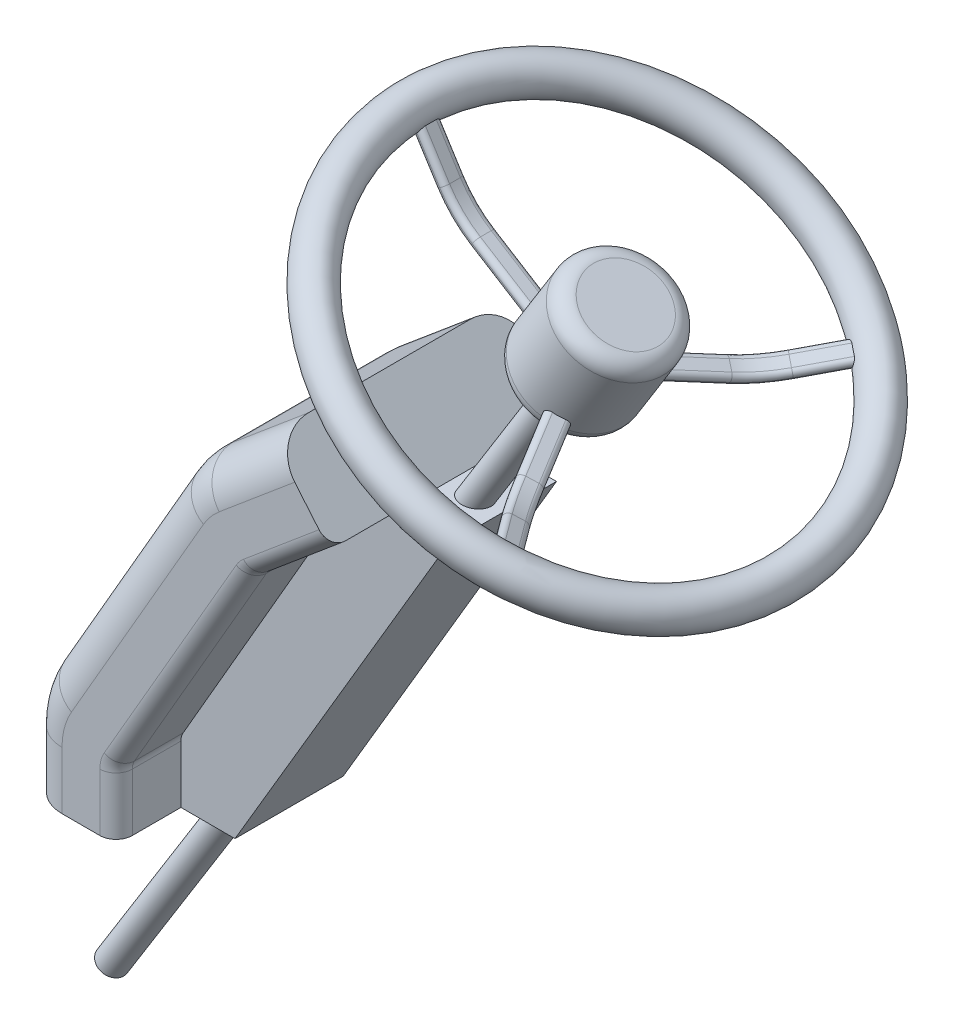
SolidWorks part; units mm, degrees
ref_plane "Front Plane" through (0, 0, 0) normal (0, 0, 1) x (1, 0, 0)
ref_plane "Top Plane" through (0, 0, 0) normal (0, 1, 0) x (1, 0, 0)
ref_plane "Right Plane" through (0, 0, 0) normal (1, 0, 0) x (0, 0, -1)
sketch "Sketch1" plane through (0, 0, 0) normal (0, 0, 1) x (1, 0, 0)
  line L0 (0, 0) -> (0, 53.2051)
  line L1 (13.3975, 103.2051) -> (135.5212, 314.7296)
  line L2 (157.845, 341.3341) -> (227.7603, 400)
  arc A0 (135.5212, 314.7296) -> (157.845, 341.3341) centre (222.1238, 264.7296) cw
  arc A1 (0, 53.2051) -> (13.3975, 103.2051) centre (100, 53.2051) cw
  point P7 (144.3376, 330)
  point P10 (0, 80)
  dimension "D6" = 100
  dimension "D1" = 250
  dimension "D2" = 400
  dimension "D3" = 30
  dimension "D4" = 20
  dimension "D5" = 80
extrude "Extrude-Thin1" add sketch "Sketch1" along normal mid plane 220 thin thin type one direction wall 85
fillet "Fillet1" radius 35 10 edges at (0, 26.6025, -110) (3.4074, 79.087, -110) (192.8027, 370.667, -110) (145.5193, 329.0084, -110) (0, 26.6025, 110) (3.4074, 79.087, 110) (192.8027, 370.667, 110) (145.5193, 329.0084, 110) (74.4593, 208.9674, -110) (74.4593, 208.9674, 110)
fillet "Fillet2" radius 15 10 edges at (85, 26.6025, -110) (85.5111, 57.0874, -110) (247.4396, 305.5533, -110) (210.6331, 274.3714, -110) (85, 26.6025, 110) (85.5111, 57.0874, 110) (247.4396, 305.5533, 110) (210.6331, 274.3714, 110) (148.0715, 166.4674, -110) (148.0715, 166.4674, 110)
sketch "Sketch2" plane through (0, 0, 0) normal (0, 0, 1) x (1, 0, 0)
  line L0 (85, 53.2051) -> (85, 0) construction
  line L1 (209.1334, 272.2296) -> (87.0096, 60.7051) construction
  line L2 (282.3973, 334.8862) -> (212.4819, 276.2203) construction
  line L3 (85, 53.2051) -> (85, 0)
  line L4 (209.1334, 272.2296) -> (87.0096, 60.7051)
  line L5 (282.3973, 334.8862) -> (212.4819, 276.2203)
  line L6 (85, 0) -> (135, 0)
  line L7 (135, 0) -> (332.3973, 334.8862)
  line L8 (332.3973, 334.8862) -> (282.3973, 334.8862)
  arc A0 (87.0096, 60.7051) -> (85, 53.2051) centre (100, 53.2051) ccw construction
  arc A1 (212.4819, 276.2203) -> (209.1334, 272.2296) centre (222.1238, 264.7296) ccw construction
  arc A2 (87.0096, 60.7051) -> (85, 53.2051) centre (100, 53.2051) ccw
  arc A3 (212.4819, 276.2203) -> (209.1334, 272.2296) centre (222.1238, 264.7296) ccw
  dimension "D1" = 50
  dimension "D2" = 50
extrude "Boss-Extrude1" add sketch "Sketch2" along normal mid plane 100
ref_plane "Plane1" through (243.0085, 390.5113, 0) normal (-0.5283, -0.849, 0) x (-0.849, 0.5283, 0)
sketch "Sketch3" plane through (243.0085, 390.5113, 0) normal (-0.5283, -0.849, 0) x (-0.849, 0.5283, 0)
  circle A0 centre (-84.0571, 0) radius 12.5
  dimension "D1" = 25
extrude "Boss-Extrude2" add sketch "Sketch3" along normal blind 649 and the other way blind 150
ref_axis "Axis1" through (399.5517, 482.9771, 0) along (-0.5283, -0.849, 0)
sketch "Sketch4" plane through (0, 0, 0) normal (0, 0, 1) x (1, 0, 0)
  line L0 (185.4582, 426.3239) -> (300.5588, 354.6987) construction
  line L1 (399.5517, 482.9771) -> (303.2876, 328.282) construction
  line L2 (393.6267, 473.4557) -> (446.4606, 558.359)
  line L3 (404.2396, 466.8514) -> (383.0137, 480.0599) construction
  line L4 (446.4606, 558.359) -> (404.0089, 584.776)
  line L5 (404.0089, 584.776) -> (351.175, 499.8726)
  line L6 (351.175, 499.8726) -> (393.6267, 473.4557)
  circle A0 centre (250.2369, 621.5752) radius 17.5
  dimension "D1" = 35
  dimension "D2" = 200
  dimension "D3" = 200
  dimension "D4" = 100
  dimension "D5" = 50
revolve "Revolve1" add sketch "Sketch4" angle 360 about axis through (399.5517, 482.9771, 0) along (-0.5283, -0.849, 0)
fillet "Fillet3" radius 15 2 edges at (351.175, 499.8726, 0) (404.0089, 584.776, 0)
sketch "Sketch6" plane through (0, 0, 0) normal (0, 0, 1) x (1, 0, 0)
  line L0 (249.7221, 621.4575) -> (280.0644, 573.5124)
  line L1 (311.7307, 542.0853) -> (360.2244, 511.9085)
  line L2 (444.0034, 459.7742) -> (359.1001, 512.6081) construction
  arc A1 (280.0644, 573.5124) -> (311.7307, 542.0853) centre (364.5646, 626.9886) ccw
  point P6 (359.1001, 512.6081)
  point P7 (359.1001, 512.6081)
  point P8 (360.2244, 511.9085)
  point P11 (292.3017, 554.1756)
  dimension "D2" = 100
  dimension "D1" = 80
sketch "Sketch7" plane through (0, 0, 0) normal (0, 0, 1) x (1, 0, 0)
extrude "Extrude-Thin2" add sketch "Sketch6" along normal mid plane 20 thin thin type one direction reverse wall 10
fillet "Fillet4" radius 5 12 edges at (269.6819, 589.9183, -10) (335.9776, 526.9969, -10) (269.6819, 589.9183, 10) (335.9776, 526.9969, 10) (277.406, 596.4128, -10) (341.261, 535.4872, -10) (277.406, 596.4128, 10) (341.261, 535.4872, 10) (294.1226, 556.0103, -10) (294.1226, 556.0103, 10) (301.1668, 563.1082, -10) (301.1668, 563.1082, 10)
pattern_circular "CirPattern1" count 3 every 120 about axis through (399.5517, 482.9771, 0) along (0.5283, 0.849, 0) of "Fillet4", "Extrude-Thin2"
